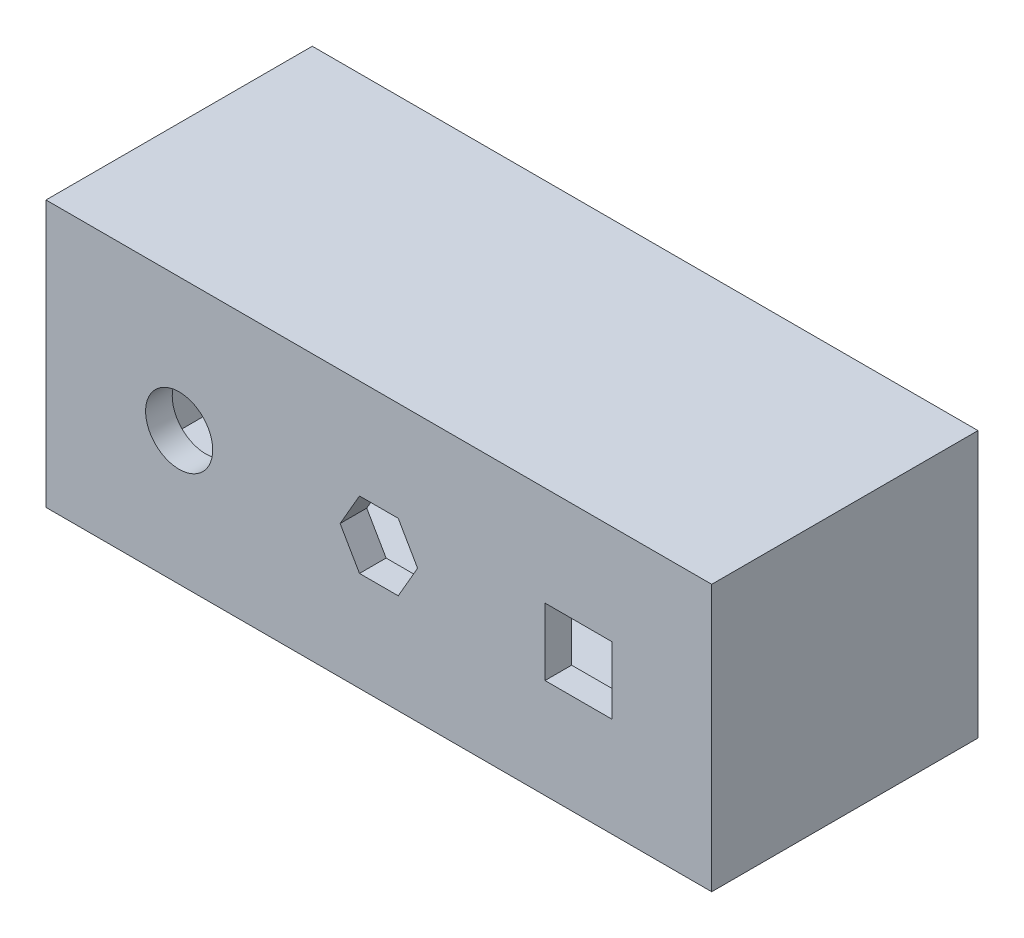
SolidWorks part; units mm, degrees
material "Beech"
ref_plane "Front Plane" through (0, 0, 0) normal (0, 0, 1) x (1, 0, 0)
ref_plane "Top Plane" through (0, 0, 0) normal (0, 1, 0) x (1, 0, 0)
ref_plane "Right Plane" through (0, 0, 0) normal (1, 0, 0) x (0, 0, -1)
sketch "Sketch5" plane through (0, 0, 0) normal (0, 0, 1) x (1, 0, 0)
  line L1 (-250, -100) -> (250, -100)
  line L2 (-250, -100) -> (-250, 100)
  line L3 (-250, 100) -> (250, 100)
  line L4 (250, -100) -> (250, 100)
  line L5 (-250, -100) -> (250, 100) construction
  line L6 (-250, 100) -> (250, -100) construction
  point P0 (0, 0)
  dimension "D1" = 200
  dimension "D2" = 500
extrude "Boss-Extrude2" add sketch "Sketch5" along normal blind 200
shell "Shell2" thickness 20 removed face at (0, 0, 0)
sketch "Sketch6" plane through (0, 0, 200) normal (0, 0, 1) x (1, 0, 0)
  line L0 (-250, 0) -> (250, 0) construction
  line L1 (14.5492, 25.2) -> (-14.5492, 25.2)
  line L2 (-14.5492, 25.2) -> (-29.0985, 0)
  line L3 (-29.0985, 0) -> (-14.5492, -25.2)
  line L4 (-14.5492, -25.2) -> (14.5492, -25.2)
  line L5 (14.5492, -25.2) -> (29.0985, 0)
  line L6 (29.0985, 0) -> (14.5492, 25.2)
  line L7 (124.8, -25.2) -> (175.2, -25.2)
  line L8 (124.8, -25.2) -> (124.8, 25.2)
  line L9 (124.8, 25.2) -> (175.2, 25.2)
  line L10 (175.2, -25.2) -> (175.2, 25.2)
  line L11 (124.8, -25.2) -> (175.2, 25.2) construction
  line L12 (124.8, 25.2) -> (175.2, -25.2) construction
  line L13 (-250, 100) -> (-250, -100) construction
  line L14 (0, -100) -> (0, 0) construction
  line L15 (-250, -100) -> (250, -100) construction
  line L16 (250, -100) -> (250, 100) construction
  circle A0 centre (0, 0) radius 25.2 construction
  circle A1 centre (-150, 0) radius 25.2
  point P11 (150, 0)
  dimension "D3" = 50.4
  dimension "D4" = 50.4
  dimension "D1" = 150
  dimension "D2" = 150
  dimension "D5" = 50.4
extrude "Cut-Extrude2" cut sketch "Sketch6" against normal blind 300
